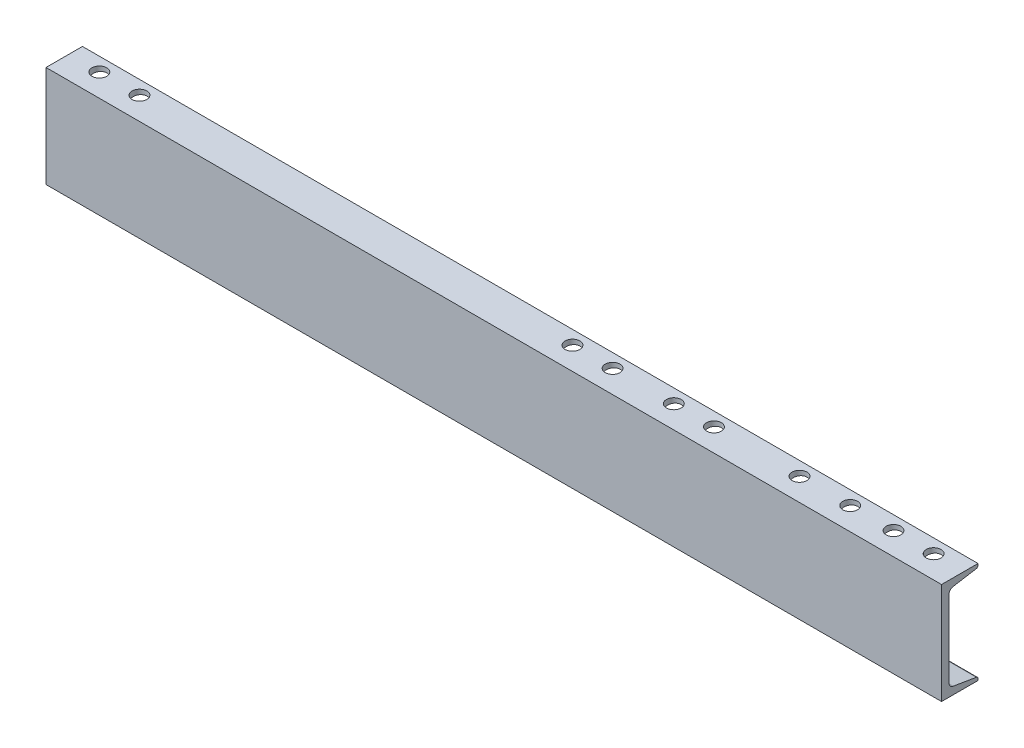
SolidWorks part; units mm, degrees
ref_plane "Front Plane" through (0, 0, 0) normal (0, 0, 1) x (1, 0, 0)
ref_plane "Top Plane" through (0, 0, 0) normal (0, 1, 0) x (1, 0, 0)
ref_plane "Right Plane" through (0, 0, 0) normal (1, 0, 0) x (0, 0, -1)
sketch "Sketch1" plane through (0, 0, 0) normal (1, 0, 0) x (0, 0, -1)
  line L0 (-27.3939, -76.2) -> (-27.3939, 76.2)
  line L1 (-27.3939, 76.2) -> (27.3939, 76.2)
  line L2 (-27.3939, -76.2) -> (27.3939, -76.2)
  line L3 (4.3561, -67.4878) -> (-21.0439, -67.4878) construction
  line L4 (-16.2941, 57.3918) -> (-16.2941, -57.3918)
  line L5 (27.3939, 76.2) -> (27.3939, 73.7107)
  line L6 (27.3939, -76.2) -> (27.3939, -73.7107)
  line L7 (-9.9269, 64.9081) -> (24.847, 70.7042)
  line L8 (-9.9269, -64.9081) -> (24.847, -70.7042)
  arc A0 (-16.2941, -57.3918) -> (-9.9269, -64.9081) centre (-8.6741, -57.3918) ccw
  arc A1 (-16.2941, 57.3918) -> (-9.9269, 64.9081) centre (-8.6741, 57.3918) cw
  arc A2 (27.3939, 73.7107) -> (24.847, 70.7042) centre (24.3459, 73.7107) cw
  arc A3 (27.3939, -73.7107) -> (24.847, -70.7042) centre (24.3459, -73.7107) ccw
extrude "Boss-Extrude1" add sketch "Sketch1" along normal mid plane 1346.2
sketch "Sketch3" plane through (0, 0, 16.2941) normal (0, 0, -1) x (-1, 0, 0)
  line L0 (-431.8, 25.4) -> (-469.9, 25.4) construction
  line L1 (-431.8, 17.4625) -> (-469.9, 17.4625)
  line L2 (-431.8, 33.3375) -> (-469.9, 33.3375)
  line L3 (-673.1, -57.3918) -> (-673.1, 57.3918) construction
  line L4 (30.1333, 0) -> (-30.1333, 0) construction
  line L5 (0, 0) -> (82.55, 0) construction
  line L6 (673.1, -57.3918) -> (673.1, 57.3918) construction
  line L7 (-673.1, 0) -> (-385.4263, 0) construction
  arc A0 (-431.8, 17.4625) -> (-431.8, 33.3375) centre (-431.8, 25.4) ccw
  arc A1 (-469.9, 33.3375) -> (-469.9, 17.4625) centre (-469.9, 25.4) ccw
  circle A2 centre (-593.725, 0) radius 12.7 construction
  circle A3 centre (82.55, 0) radius 9.525
  circle A4 centre (31.75, 0) radius 9.525
  point P3 (-450.85, 25.4)
  dimension "D4" = 25.4
  dimension "D7" = 19.05
  dimension "D8" = 50.8
  dimension "D1" = 15.875
  dimension "D2" = 38.1
  dimension "D3" = 203.2
  dimension "D5" = 79.375
  dimension "D6" = 590.55
  dimension "D9" = 25.4
sketch "Sketch5" plane through (0, -76.2, 0) normal (0, -1, 0) x (1, 0, 0)
  line L0 (687.9131, -6.7373) -> (124.9749, -6.7373) construction
  line L2 (673.1, 27.3939) -> (673.1, -27.3939) construction
  line L3 (-673.1, 27.3939) -> (-673.1, -27.3939) construction
  line L5 (673.1, 27.3939) -> (-673.1, 27.3939) construction
  circle A0 centre (627.0625, -6.7373) radius 11.1125
  circle A1 centre (566.7375, -6.7374) radius 11.1125
  circle A2 centre (296.8625, -6.7373) radius 11.1125
  circle A3 centre (236.5375, -6.7374) radius 11.1125
  circle A4 centre (84.1375, -6.7374) radius 11.1125
  circle A5 centre (144.4625, -6.7373) radius 11.1125
  circle A6 centre (-627.0625, -6.7373) radius 11.1125
  circle A7 centre (-566.7375, -6.7373) radius 11.1125
  circle A8 centre (501.65, -6.7373) radius 11.1125
  circle A9 centre (425.45, -6.7373) radius 11.1125
  dimension "D2" = 22.225
  dimension "D4" = 60.325
  dimension "D12" = 1098.55
  dimension "D13" = 76.2
  dimension "D14" = 22.225
  dimension "D15" = 22.225
  dimension "D3" = 46.0375
  dimension "D6" = 330.2
  dimension "D8" = 482.6
  dimension "D10" = 46.0375
  dimension "D11" = 34.1313
  dimension "D5" = 2
  dimension "D7" = 2
  dimension "D9" = 2
extrude "Cut-Extrude3" cut sketch "Sketch5" against normal up to surface (152.4 mm away) up to face at (0, 76.2, 0)
